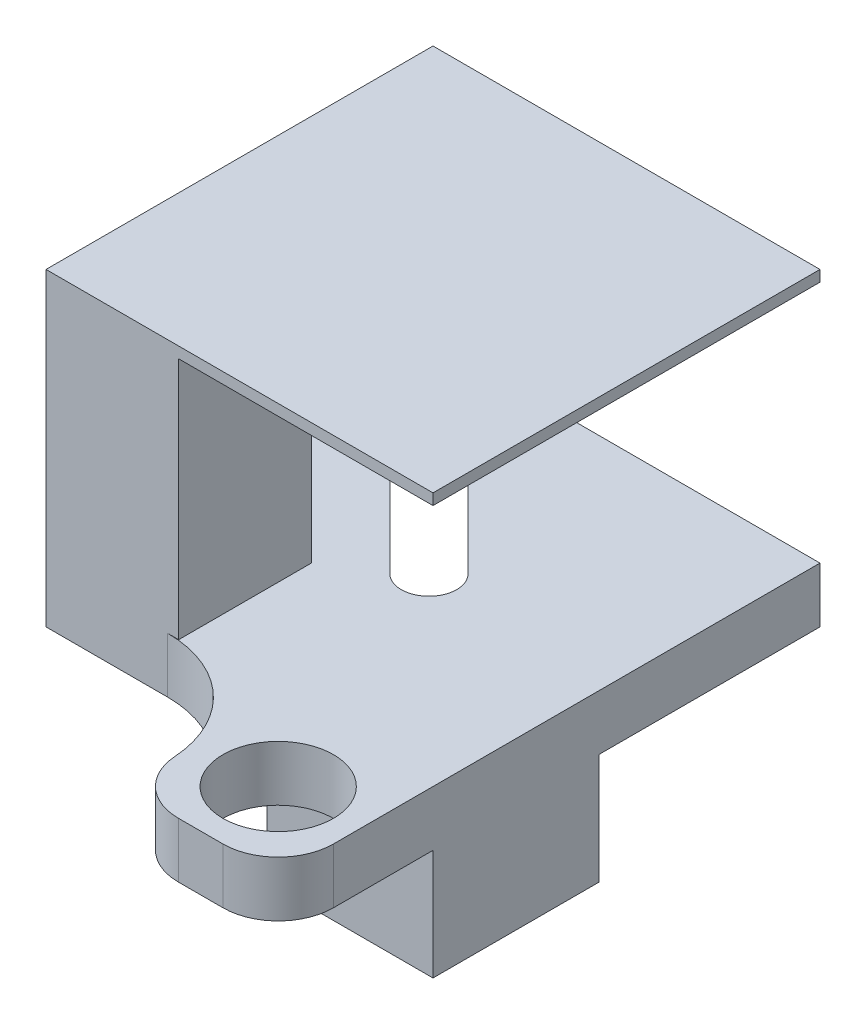
SolidWorks part; units mm, degrees
ref_plane "Front Plane" through (0, 0, 0) normal (0, 0, 1) x (1, 0, 0)
ref_plane "Top Plane" through (0, 0, 0) normal (0, 1, 0) x (1, 0, 0)
ref_plane "Right Plane" through (0, 0, 0) normal (1, 0, 0) x (0, 0, -1)
sketch "Sketch1" plane through (0, 0, 0) normal (0, 1, 0) x (1, 0, 0)
  line L2 (0, 0) -> (0, 35)
  line L10 (35, 35) -> (35, 0)
  line L11 (35, 35) -> (0, 35)
  line L13 (5.7773, 32.3996) -> (19.9194, 18.2575)
  line L15 (16.213, 14.9015) -> (2.0709, 29.0437)
  line L17 (35, 0) -> (35, -14)
  line L18 (35, -14) -> (21, -14)
  line L19 (21, -14) -> (21, 0)
  line L20 (21, 0) -> (0, 0)
  arc A2 (16.213, 14.9015) -> (19.9194, 18.2575) centre (18.1495, 16.4876) ccw
  arc A3 (5.7773, 32.3996) -> (2.0709, 29.0437) centre (3.8408, 30.8136) ccw
  circle A4 centre (28, -7) radius 5
  dimension "D3" = 10
  dimension "D4" = 14
  dimension "D7" = 7
  dimension "D8" = 7
  dimension "D1" = 35
  dimension "D2" = 35
  dimension "D5" = 5
  dimension "D6" = 20
  dimension "D9" = 14
  dimension "D10" = 45
  dimension "D11" = 45
extrude "Boss-Extrude1" add sketch "Sketch1" along normal blind 5
sketch "Sketch2" plane through (0, 0, 0) normal (0, -1, 0) x (1, 0, 0)
  line L3 (30, -5) -> (20, -5)
  line L4 (20, 0) -> (20, -5)
  line L7 (35, -15) -> (30, -15)
  line L8 (30, -5) -> (30, -15)
  line L20 (35, -15) -> (35, 0)
  line L21 (0, 0) -> (21, 0) construction
  line L22 (35, 0) -> (20, 0)
  line L23 (35, 14) -> (35, -35) construction
  dimension "D1" = 5
  dimension "D2" = 5
  dimension "D3" = 10
  dimension "D4" = 10
  dimension "D5" = 0
  dimension "D6" = 0
extrude "Boss-Extrude2" add sketch "Sketch2" along normal blind 10
sketch "Sketch3" plane through (0, 5, 0) normal (0, 1, 0) x (1, 0, 0)
  line L1 (0, 0) -> (12, 0)
  line L2 (0, 0) -> (0, 12)
  line L3 (0, 12) -> (12, 12)
  line L4 (12, 0) -> (12, 12)
  dimension "D1" = 12
extrude "Boss-Extrude3" add sketch "Sketch3" along normal blind 22
sketch "Sketch4" plane through (0, 27, 0) normal (0, 1, 0) x (1, 0, 0)
  line L1 (0, 0) -> (35, 0)
  line L2 (0, 0) -> (0, 35)
  line L3 (0, 35) -> (35, 35)
  line L4 (35, 0) -> (35, 35)
extrude "Boss-Extrude4" add sketch "Sketch4" along normal blind 1
sketch "Sketch5" [suppressed] plane through (0, 20, 0) normal (0, 1, 0) x (1, 0, 0)
  line L0 (0, 0) -> (35, 0) construction
  line L3 (0, 35) -> (0, 0) construction
  circle A0 centre (17.5, 17.5) radius 10
  dimension "D1" = 17.5
  dimension "D2" = 17.5
  dimension "D3" = 20
extrude "Boss-Extrude5" [suppressed] add sketch "Sketch5" along normal blind 50
sketch "Sketch6" [suppressed] plane through (0, 70, 0) normal (0, 1, 0) x (1, 0, 0)
  line L6 (7.5, 17.5) -> (7.5, -32.5)
  line L7 (7.5, -32.5) -> (27.5, -32.5)
  line L8 (27.5, 17.5) -> (27.5, -32.5)
  arc A1 (27.5, 17.5) -> (7.5, 17.5) centre (17.5, 17.5) ccw
  dimension "D1" = 50
extrude "Boss-Extrude6" [suppressed] add sketch "Sketch6" along normal blind 5
fillet "Fillet1" radius 10 1 edges at (21, 2.5, 0)
fillet "Fillet4" radius 5 2 edges at (35, 2.5, 14) (21, 2.5, 14)
